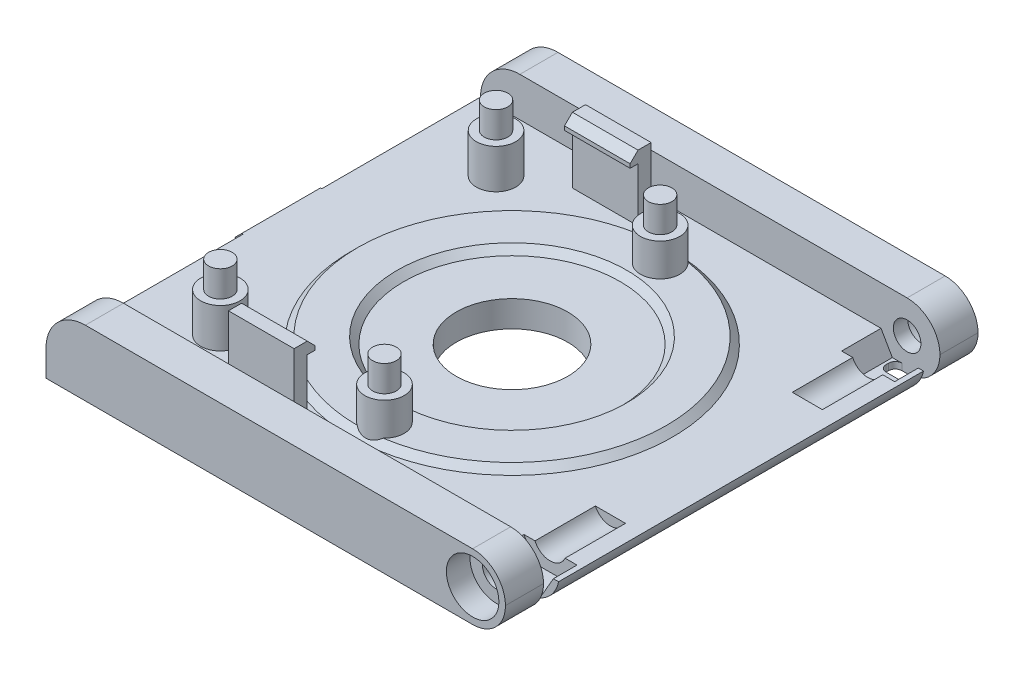
SolidWorks part; units mm, degrees
ref_plane "前视基准面" through (0, 0, 0) normal (0, 0, 1) x (1, 0, 0)
ref_plane "上视基准面" through (0, 0, 0) normal (0, 1, 0) x (1, 0, 0)
ref_plane "右视基准面" through (0, 0, 0) normal (1, 0, 0) x (0, 0, -1)
sketch "zero" plane through (0, 0, 0) normal (0, 1, 0) x (1, 0, 0)
  line L1 (-29.5, 15) -> (29.5, 15)
  line L2 (-32.5, 12) -> (-32.5, -12)
  line L3 (-29.5, -15) -> (29.5, -15)
  line L4 (32.5, 12) -> (32.5, -12)
  line L5 (-32.5, 15) -> (32.5, -15) construction
  line L6 (-32.5, -15) -> (32.5, 15) construction
  line L7 (-25.7, -15) -> (-14.5, -15)
  line L8 (-25.7, -15) -> (-25.7, -9.6569)
  line L9 (-25.7, -9.6569) -> (-14.5, -9.6569)
  line L10 (-14.5, -15) -> (-14.5, -9.6569)
  line L11 (5.2, -15) -> (12.7, -15)
  line L12 (5.2, -15) -> (5.2, -11)
  line L13 (5.2, -11) -> (12.7, -11)
  line L14 (12.7, -15) -> (12.7, -11)
  line L15 (17.8, -15) -> (25.3, -15)
  line L16 (17.8, -15) -> (17.8, -11)
  line L17 (17.8, -11) -> (25.3, -11)
  line L18 (25.3, -15) -> (25.3, -11)
  line L19 (-32.5, 7.7) -> (-19.5, 7.7)
  line L20 (-32.5, 7.7) -> (-32.5, -4.3)
  line L21 (-32.5, -4.3) -> (-19.5, -4.3)
  line L22 (-19.5, 7.7) -> (-19.5, -4.3)
  line L23 (-25.5, 14) -> (25.5, 14)
  line L24 (-25.5, 14) -> (-25.5, 8.8)
  line L25 (-25.5, 8.8) -> (25.5, 8.8)
  line L26 (25.5, 14) -> (25.5, 8.8)
  line L27 (-19.5, 7.2329) -> (-35.5, 7.2329)
  line L28 (-19.5, 7.2329) -> (-19.5, -3.7671)
  line L29 (-19.5, -3.7671) -> (-35.5, -3.7671)
  line L30 (-35.5, 7.2329) -> (-35.5, -3.7671)
  arc A0 (29.5, -15) -> (32.5, -12) centre (29.5, -12) ccw
  arc A1 (29.5, 15) -> (32.5, 12) centre (29.5, 12) cw
  arc A2 (-32.5, -12) -> (-29.5, -15) centre (-29.5, -12) ccw
  arc A3 (-29.5, 15) -> (-32.5, 12) centre (-29.5, 12) ccw
  circle A4 centre (-29, 11.4) radius 3
  circle A5 centre (-29, -11.5) radius 3
  circle A6 centre (29, 11.4) radius 3
  circle A7 centre (29, -11.5) radius 3
  circle A8 centre (-29, 11.4) radius 1.375
  circle A9 centre (-29, -11.5) radius 1.375
  circle A10 centre (29, -11.5) radius 1.375
  circle A11 centre (29, 11.4) radius 1.375
  point P0 (0, 0)
  dimension "D3" = 3
  dimension "D4" = 6
  dimension "D9" = 2.75
  dimension "D1" = 65
  dimension "D2" = 30
  dimension "D5" = 3.6
  dimension "D6" = 3.5
  dimension "D7" = 3.5
  dimension "D8" = 3.5
  dimension "D10" = 12
  dimension "D11" = 7.3
  dimension "D12" = 13
  dimension "D13" = 11.2
  dimension "D14" = 6.8
  dimension "D15" = 19.7
  dimension "D16" = 7.5
  dimension "D17" = 7.5
  dimension "D18" = 5.1
  dimension "D19" = 4
  dimension "D20" = 5.2
  dimension "D21" = 7
  dimension "D22" = 7
  dimension "D23" = 1
  dimension "D24" = 11
  dimension "D25" = 16
sketch "sugar" plane through (0, 0, 0) normal (0, 1, 0) x (1, 0, 0)
  line L1 (-29.5, 15) -> (29.5, 15)
  line L2 (-32.5, 12) -> (-32.5, -12)
  line L3 (-29.5, -15) -> (29.5, -15)
  line L4 (32.5, 12) -> (32.5, -12)
  line L5 (-32.5, 15) -> (32.5, -15) construction
  line L6 (-32.5, -15) -> (32.5, 15) construction
  line L7 (23.5, -11.5) -> (19.5, -11.5)
  line L8 (23.5, -11.5) -> (23.5, -13.9082)
  line L9 (23.5, -13.9082) -> (19.5, -13.9082)
  line L10 (19.5, -11.5) -> (19.5, -13.9082)
  line L11 (16, -11.0071) -> (8.5, -11.0071)
  line L12 (16, -11.0071) -> (16, -15)
  line L13 (16, -15) -> (8.5, -15)
  line L14 (8.5, -11.0071) -> (8.5, -15)
  line L15 (20.5, -13.9082) -> (22.5, -13.9082)
  line L16 (20.5, -13.9082) -> (20.5, -14.8173)
  line L17 (20.5, -14.8173) -> (22.5, -14.8173)
  line L18 (22.5, -13.9082) -> (22.5, -14.8173)
  arc A0 (29.5, 15) -> (32.5, 12) centre (29.5, 12) cw
  arc A1 (29.5, -15) -> (32.5, -12) centre (29.5, -12) ccw
  arc A2 (-32.5, -12) -> (-29.5, -15) centre (-29.5, -12) ccw
  arc A3 (-29.5, 15) -> (-32.5, 12) centre (-29.5, 12) ccw
  circle A4 centre (-29, 11.4) radius 3
  circle A5 centre (-29, 11.4) radius 1.375
  circle A6 centre (-29, -11.5) radius 3
  circle A7 centre (-29, -11.5) radius 1.375
  circle A8 centre (29, 11.4) radius 3
  circle A9 centre (29, 11.4) radius 1.375
  circle A10 centre (29, -11.5) radius 3
  circle A11 centre (29, -11.5) radius 1.375
  dimension "D3" = 3
  dimension "D1" = 65
  dimension "D2" = 30
  dimension "D4" = 9
  dimension "D5" = 4
  dimension "D6" = 3.5
  dimension "D7" = 7.5
  dimension "D8" = 2
  dimension "D9" = 1
sketch "case" plane through (0, 0, 0) normal (0, 1, 0) x (1, 0, 0)
  line L1 (-34.0422, 18) -> (30.9578, 18)
  line L2 (-39.0422, 13) -> (-39.0422, -13)
  line L3 (-34.0422, -18) -> (30.9578, -18)
  line L4 (35.9578, 13) -> (35.9578, -13)
  line L5 (-39.0422, 18) -> (35.9578, -18) construction
  line L6 (-39.0422, -18) -> (35.9578, 18) construction
  arc A0 (-39.0422, -13) -> (-34.0422, -18) centre (-34.0422, -13) ccw
  arc A1 (30.9578, -18) -> (35.9578, -13) centre (30.9578, -13) ccw
  arc A2 (30.9578, 18) -> (35.9578, 13) centre (30.9578, 13) cw
  arc A3 (-34.0422, 18) -> (-39.0422, 13) centre (-34.0422, 13) ccw
  point P0 (-1.5422, 0)
  point P3 (-1.5422, 0)
  dimension "D3" = 5
  dimension "D1" = 75
  dimension "D2" = 36
extrude "凸台-拉伸2" add sketch "case" along normal blind 7
sketch "草图2" plane through (0, 0, 0) normal (0, 1, 0) x (1, 0, 0)
  line L4 (-34.0422, -15.1) -> (30.9578, -15.1)
  line L5 (33.0578, -13) -> (33.0578, 13)
  line L6 (30.9578, 15.1) -> (-34.0422, 15.1)
  line L7 (-36.1422, 13) -> (-36.1422, -13)
  line L12 (33.8578, -13) -> (33.8578, 13)
  line L13 (30.9578, 15.9) -> (-34.0422, 15.9)
  line L14 (-36.9422, 13) -> (-36.9422, -13)
  line L15 (-34.0422, -15.9) -> (30.9578, -15.9)
  arc A4 (30.9578, -15.1) -> (33.0578, -13) centre (30.6746, -12.7168) ccw
  arc A5 (33.0578, 13) -> (30.9578, 15.1) centre (30.6746, 12.7168) ccw
  arc A6 (-34.0422, 15.1) -> (-36.1422, 13) centre (-33.759, 12.7168) ccw
  arc A7 (-36.1422, -13) -> (-34.0422, -15.1) centre (-33.759, -12.7168) ccw
  arc A12 (30.9578, -15.9) -> (33.8578, -13) centre (30.5796, -12.6217) ccw
  arc A13 (33.8578, 13) -> (30.9578, 15.9) centre (30.5796, 12.6217) ccw
  arc A14 (-34.0422, 15.9) -> (-36.9422, 13) centre (-33.6639, 12.6217) ccw
  arc A15 (-36.9422, -13) -> (-34.0422, -15.9) centre (-33.6639, -12.6217) ccw
ref_plane "基准面1" through (0, 7, 0) normal (0, 1, 0) x (1, 0, 0)
sketch "草图3" plane through (0, 7, 0) normal (0, 1, 0) x (1, 0, 0)
  line L4 (-34.0422, -15.1) -> (30.9578, -15.1)
  line L5 (33.0578, -13) -> (33.0578, 13)
  line L6 (30.9578, 15.1) -> (-34.0422, 15.1)
  line L7 (-36.1422, 13) -> (-36.1422, -13)
  line L8 (-34.0422, -15.1) -> (30.9578, -15.1)
  line L9 (33.0578, -13) -> (33.0578, 13)
  line L10 (30.9578, 15.1) -> (-34.0422, 15.1)
  line L11 (-36.1422, 13) -> (-36.1422, -13)
  line L12 (-36.9422, 13) -> (-36.9422, -13)
  line L13 (-34.0422, -15.9) -> (30.9578, -15.9)
  line L14 (33.8578, -13) -> (33.8578, 13)
  line L15 (30.9578, 15.9) -> (-34.0422, 15.9)
  line L16 (-36.9422, 13) -> (-36.9422, -13)
  line L17 (-34.0422, -15.9) -> (30.9578, -15.9)
  line L18 (33.8578, -13) -> (33.8578, 13)
  line L19 (30.9578, 15.9) -> (-34.0422, 15.9)
  arc A4 (30.9578, -15.1) -> (33.0578, -13) centre (30.6746, -12.7168) ccw
  arc A5 (33.0578, 13) -> (30.9578, 15.1) centre (30.6746, 12.7168) ccw
  arc A6 (-34.0422, 15.1) -> (-36.1422, 13) centre (-33.759, 12.7168) ccw
  arc A7 (-36.1422, -13) -> (-34.0422, -15.1) centre (-33.759, -12.7168) ccw
  arc A8 (30.9578, -15.1) -> (33.0578, -13) centre (30.6746, -12.7168) ccw
  arc A9 (33.0578, 13) -> (30.9578, 15.1) centre (30.6746, 12.7168) ccw
  arc A10 (-34.0422, 15.1) -> (-36.1422, 13) centre (-33.759, 12.7168) ccw
  arc A11 (-36.1422, -13) -> (-34.0422, -15.1) centre (-33.759, -12.7168) ccw
  arc A12 (-36.9422, -13) -> (-34.0422, -15.9) centre (-33.6639, -12.6217) ccw
  arc A13 (30.9578, -15.9) -> (33.8578, -13) centre (30.5796, -12.6217) ccw
  arc A14 (33.8578, 13) -> (30.9578, 15.9) centre (30.5796, 12.6217) ccw
  arc A15 (-34.0422, 15.9) -> (-36.9422, 13) centre (-33.6639, 12.6217) ccw
  arc A16 (-36.9422, -13) -> (-34.0422, -15.9) centre (-33.6639, -12.6217) ccw
  arc A17 (30.9578, -15.9) -> (33.8578, -13) centre (30.5796, -12.6217) ccw
  arc A18 (33.8578, 13) -> (30.9578, 15.9) centre (30.5796, 12.6217) ccw
  arc A19 (-34.0422, 15.9) -> (-36.9422, 13) centre (-33.6639, 12.6217) ccw
  dimension "D1" = 0
  dimension "D2" = 0
extrude "凸台-拉伸4" add sketch "草图3" along normal blind 1
ref_plane "基准面3" through (33.8578, 0, 0) normal (1, 0, 0) x (0, 0, -1)
sketch "草图7" plane through (0, 7, 0) normal (0, 1, 0) x (1, 0, 0)
  line L0 (-36.9422, 13) -> (-36.9422, -13) construction
  line L1 (-36.9422, 5) -> (-36.1422, 5)
  line L2 (-36.9422, 5) -> (-36.9422, -5)
  line L3 (-36.9422, -5) -> (-36.1422, -5)
  line L4 (-36.1422, 5) -> (-36.1422, -5)
  line L5 (-36.1422, 13) -> (-36.1422, -13) construction
  point P10 (-36.1422, 0)
  dimension "D1" = 5
  dimension "D2" = 10
extrude "凸台-拉伸8" add sketch "草图7" along normal blind 2.8
ref_plane "基准面5" through (0, 0, 5) normal (0, 0, 1) x (1, 0, 0)
sketch "草图8" plane through (0, 0, 5) normal (0, 0, 1) x (1, 0, 0)
  line L0 (-34.0422, 7) -> (-39.0422, 7) construction
  line L1 (-36.9422, 9.8) -> (-36.9422, 8) construction
  circle A0 centre (-36.6922, 8.6) radius 0.7
  dimension "D1" = 1.4
  dimension "D2" = 1.6
  dimension "D3" = 0.25
extrude "凸台-拉伸9" add sketch "草图8" against normal blind 10
fillet "圆角3" radius 0.5 1 edges at (-36.9422, 9.8, 0)
sketch "草图13" plane through (0, 8, 0) normal (0, 1, 0) x (1, 0, 0)
  line L0 (-36.9422, -5) -> (-36.9422, -13) construction
  line L1 (-36.1422, -5) -> (-36.9422, -5)
  line L2 (-36.1422, -5) -> (-36.1422, -7)
  line L3 (-36.1422, -7) -> (-36.9422, -7)
  line L4 (-36.9422, -5) -> (-36.9422, -7)
  line L5 (-36.9422, 13) -> (-36.9422, 5) construction
  line L6 (-36.1422, 5) -> (-36.9422, 5)
  line L7 (-36.1422, 5) -> (-36.1422, 7)
  line L8 (-36.1422, 7) -> (-36.9422, 7)
  line L9 (-36.9422, 5) -> (-36.9422, 7)
  dimension "D1" = 2
  dimension "D2" = 2
extrude "切除-拉伸2" cut sketch "草图13" against normal blind 1
sketch "草图15" plane through (0, 7, 0) normal (0, 1, 0) x (1, 0, 0)
  line L4 (-34.0422, -15.1) -> (30.9578, -15.1)
  line L5 (33.0578, -13) -> (33.0578, 13)
  line L6 (30.9578, 15.1) -> (-34.0422, 15.1)
  line L7 (-36.1422, 13) -> (-36.1422, -13)
  line L8 (-34.0422, -15.1) -> (30.9578, -15.1)
  line L9 (33.0578, -13) -> (33.0578, 13)
  line L10 (30.9578, 15.1) -> (-34.0422, 15.1)
  line L11 (-36.1422, 13) -> (-36.1422, -13)
  arc A4 (30.9578, -15.1) -> (33.0578, -13) centre (30.6746, -12.7168) ccw
  arc A5 (33.0578, 13) -> (30.9578, 15.1) centre (30.6746, 12.7168) ccw
  arc A6 (-34.0422, 15.1) -> (-36.1422, 13) centre (-33.759, 12.7168) ccw
  arc A7 (-36.1422, -13) -> (-34.0422, -15.1) centre (-33.759, -12.7168) ccw
  arc A8 (30.9578, -15.1) -> (33.0578, -13) centre (30.6746, -12.7168) ccw
  arc A9 (33.0578, 13) -> (30.9578, 15.1) centre (30.6746, 12.7168) ccw
  arc A10 (-34.0422, 15.1) -> (-36.1422, 13) centre (-33.759, 12.7168) ccw
  arc A11 (-36.1422, -13) -> (-34.0422, -15.1) centre (-33.759, -12.7168) ccw
  dimension "D1" = 0
extrude "切除-拉伸3" cut sketch "草图15" against normal blind 5
sketch "草图19" plane through (0, 2, 0) normal (0, 1, 0) x (1, 0, 0)
  line L0 (30.9578, 18) -> (-34.0422, 18) construction
  circle A0 centre (-1.5422, 0) radius 4.25
  point P5 (-1.5422, 18)
  dimension "D1" = 8.5
extrude "切除-拉伸4" cut sketch "草图19" against normal blind 3
sketch "草图21" plane through (0, 2, 0) normal (0, 1, 0) x (1, 0, 0)
  line L0 (-34.0422, -15.1) -> (30.9578, -15.1) construction
  line L1 (30.9578, 15.1) -> (-34.0422, 15.1) construction
  line L5 (30.9578, 15.1) -> (-34.0422, 15.1) construction
  line L6 (-34.0422, -15.1) -> (30.9578, -15.1) construction
  circle A0 centre (-13.2575, 10.5) radius 1.5
  circle A1 centre (-0.7575, 10.5) radius 1.5
  circle A2 centre (-13.2575, -10.5) radius 1.5
  circle A3 centre (-0.7575, -10.5) radius 1.5
  circle A4 centre (-1.5422, 0) radius 4.25 construction
  dimension "D1" = 3
  dimension "D2" = 12.5
  dimension "D3" = 12.5
  dimension "D4" = 4.6
  dimension "D5" = 4.6
  dimension "D7" = 11.7153
  dimension "D8" = 4.6
  dimension "D9" = 4.6
extrude "凸台-拉伸11" add sketch "草图21" along normal blind 3
sketch "草图22" plane through (0, 5, 0) normal (0, 1, 0) x (1, 0, 0)
  circle A0 centre (-13.2575, -10.5) radius 0.9
  circle A1 centre (-0.7575, -10.5) radius 0.9
  circle A2 centre (-13.2575, 10.5) radius 0.9
  circle A3 centre (-0.7575, 10.5) radius 0.9
  circle A4 centre (-13.2575, 10.5) radius 1.5 construction
  circle A5 centre (-13.2575, -10.5) radius 1.5 construction
  circle A6 centre (-0.7575, -10.5) radius 1.5 construction
  circle A7 centre (-0.7575, 10.5) radius 1.5 construction
  dimension "D1" = 1.8
extrude "凸台-拉伸12" add sketch "草图22" along normal blind 2
sketch "草图28" plane through (0, 2, 0) normal (0, 1, 0) x (1, 0, 0)
  line L0 (30.9578, 15.1) -> (-34.0422, 15.1) construction
  line L1 (-4.5422, -12.6) -> (-9.5422, -12.6)
  line L2 (-4.5422, -12.6) -> (-4.5422, -13.6)
  line L3 (-4.5422, -13.6) -> (-9.5422, -13.6)
  line L4 (-9.5422, -12.6) -> (-9.5422, -13.6)
  line L5 (-4.5422, 13.6) -> (-9.5422, 13.6)
  line L6 (-4.5422, 13.6) -> (-4.5422, 12.6)
  line L7 (-4.5422, 12.6) -> (-9.5422, 12.6)
  line L8 (-9.5422, 13.6) -> (-9.5422, 12.6)
  line L9 (-34.0422, -15.1) -> (30.9578, -15.1) construction
  circle A0 centre (-1.5422, 0) radius 4.25 construction
  dimension "D1" = 1
  dimension "D2" = 1.5
  dimension "D3" = 5
  dimension "D4" = 1.5
  dimension "D5" = 3
extrude "凸台-拉伸16" add sketch "草图28" along normal blind 5
fillet "圆角4" radius 1 2 edges at (-7.0422, 2, -13.6) (-7.0422, 2, 13.6)
sketch "草图29" plane through (0, 0, 12.6) normal (0, 0, -1) x (-1, 0, 0)
  line L0 (9.5422, 7) -> (9.5422, 2) construction
  line L1 (4.5422, 7) -> (9.5422, 7)
  line L2 (4.5422, 7) -> (4.5422, 6.1)
  line L3 (4.5422, 6.1) -> (9.5422, 6.1)
  line L4 (9.5422, 7) -> (9.5422, 6.1)
  dimension "D1" = 0.9
extrude "凸台-拉伸17" add sketch "草图29" along normal blind 0.6
sketch "草图30" plane through (0, 0, -12.6) normal (0, 0, 1) x (1, 0, 0)
  line L0 (-4.5422, 7) -> (-4.5422, 2) construction
  line L1 (-9.5422, 7) -> (-4.5422, 7)
  line L2 (-9.5422, 7) -> (-9.5422, 6.1)
  line L3 (-9.5422, 6.1) -> (-4.5422, 6.1)
  line L4 (-4.5422, 7) -> (-4.5422, 6.1)
  dimension "D1" = 0.9
extrude "凸台-拉伸18" add sketch "草图30" along normal blind 0.6
chamfer "倒角5" distance 0.6 angle 45 2 edges at (-7.0422, 7, -12) (-7.0422, 7, 12)
sketch "草图32" plane through (0, 0, 0) normal (0, 1, 0) x (1, 0, 0)
  line L75 (-14.6761, -9.5363) -> (-15.4836, -9.6938)
  line L76 (-12.4748, -8.5613) -> (-14.1869, -8.5613)
  line L77 (-12.4748, -7.6298) -> (-12.4748, -8.5613)
  line L78 (-15.4702, -7.6298) -> (-12.4748, -7.6298)
  line L79 (-15.4702, -8.3938) -> (-15.4702, -7.6298)
  line L80 (-14.9509, -8.4574) -> (-15.4702, -8.3938)
  line L81 (-14.9509, -8.4776) -> (-14.9509, -8.4574)
  line L82 (-13.8452, -6.0752) -> (-13.366, -6.0752)
  line L83 (-12.4748, -7.0133) -> (-14.1769, -7.0133)
  line L84 (-12.4748, -6.2494) -> (-12.4748, -7.0133)
  line L85 (-12.7763, -6.1824) -> (-12.4748, -6.2494)
  line L86 (-12.7763, -6.1589) -> (-12.7763, -6.1824)
  line L87 (-15.1519, -4.5104) -> (-14.5354, -4.8388)
  line L88 (-12.3475, -2.6743) -> (-12.3475, -2.9592)
  line L89 (-12.5853, -1.763) -> (-12.5586, -1.763)
  line L90 (-13.681, -1.8199) -> (-13.6609, -1.8199)
  line L91 (-15.4702, -4.2424) -> (-15.4702, -3.1434)
  line L92 (-14.7934, -4.2424) -> (-15.4702, -4.2424)
  line L93 (-14.7934, -3.78) -> (-14.7934, -4.2424)
  line L94 (-13.0645, -3.1367) -> (-13.0645, -2.6643)
  line L95 (-15.4702, -0.8717) -> (-15.4702, 0.0664)
  line L96 (-12.4748, -0.8717) -> (-15.4702, -0.8717)
  line L97 (-12.4748, -0.1078) -> (-12.4748, -0.8717)
  line L98 (-12.8869, -0.0408) -> (-12.4748, -0.1078)
  line L99 (-12.8869, -0.0207) -> (-12.8869, -0.0408)
  line L100 (-15.4702, 1.849) -> (-13.6173, 1.849)
  line L101 (-15.4702, 0.9141) -> (-15.4702, 1.849)
  line L102 (-13.7346, 0.9141) -> (-15.4702, 0.9141)
  line L103 (-15.4702, 0.0664) -> (-13.5068, 0.0664)
  line L104 (-13.614, 4.7204) -> (-12.964, 5.2531)
  line L105 (-14.207, 4.3083) -> (-13.9959, 3.809)
  line L106 (-15.3596, 2.8776) -> (-15.9493, 2.4085)
  line L107 (-14.7029, 3.0686) -> (-14.8973, 3.5577)
  line L108 (-15.3362, 5.8361) -> (-15.3362, 6.3153)
  line L109 (-12.4748, 5.8361) -> (-15.3362, 5.8361)
  line L110 (-12.4748, 6.3153) -> (-12.4748, 5.8361)
  line L111 (-15.3362, 6.3153) -> (-12.4748, 6.3153)
  line L112 (-15.9393, 9.0091) -> (-15.9393, 8.4529)
  line L113 (-14.4014, 9.0091) -> (-15.9393, 9.0091)
  line L114 (-14.4014, 8.4328) -> (-14.4014, 9.0091)
  line L115 (-14.006, 9.0091) -> (-14.006, 8.3692)
  line L116 (-12.4748, 9.0091) -> (-14.006, 9.0091)
  line L117 (-12.4748, 9.4984) -> (-12.4748, 9.0091)
  line L118 (-16.3346, 9.4984) -> (-12.4748, 9.4984)
  line L119 (-16.3346, 8.396) -> (-16.3346, 9.4984)
  spline S0 degree 3 poles (-15.4836, -9.6938) (-15.5205, -9.61) (-15.5439, -9.5095) (-15.5439, -9.3319) knots 10 10 10 10 11 11 11 11
  spline S1 degree 3 poles (-14.723, -9.208) (-14.723, -9.342) (-14.7029, -9.4291) (-14.6761, -9.5363) knots 8 8 8 8 9 9 9 9
  spline S2 degree 3 poles (-14.1869, -8.5613) (-14.5823, -8.7188) (-14.723, -8.9869) (-14.723, -9.208) knots 7 7 7 7 8 8 8 8
  spline S3 degree 3 poles (-15.5439, -9.3319) (-15.5439, -9.0304) (-15.3496, -8.6987) (-14.9509, -8.4776) knots 0 0 0 0 1 1 1 1
  spline S4 degree 3 poles (-13.3861, -5.3012) (-13.5972, -5.3012) (-13.7648, -5.4922) (-13.8452, -6.0752) knots 2 2 2 2 3 3 3 3
  spline S5 degree 3 poles (-13.1282, -5.6229) (-13.1282, -5.4285) (-13.2119, -5.3012) (-13.3861, -5.3012) knots 1 1 1 1 2 2 2 2
  spline S6 degree 3 poles (-13.366, -6.0752) (-13.2186, -5.9378) (-13.1282, -5.8138) (-13.1282, -5.6229) knots 0 0 0 0 1 1 1 1
  spline S7 degree 3 poles (-14.1769, -7.0133) (-15.1151, -7.0133) (-15.5439, -6.5744) (-15.5439, -5.8004) knots 11 11 11 11 12 12 12 12
  spline S8 degree 3 poles (-12.4011, -5.3012) (-12.4011, -5.6329) (-12.5552, -5.911) (-12.7763, -6.1589) knots 6 6 6 6 7 7 7 7
  spline S9 degree 3 poles (-13.3124, -4.4099) (-12.8132, -4.4099) (-12.4011, -4.7483) (-12.4011, -5.3012) knots 5 5 5 5 6 6 6 6
  spline S10 degree 3 poles (-14.4148, -6.0752) (-14.2874, -4.9058) (-13.9457, -4.4099) (-13.3124, -4.4099) knots 4 4 4 4 5 5 5 5
  spline S11 degree 3 poles (-14.7967, -5.6229) (-14.7967, -5.9277) (-14.656, -6.0551) (-14.4148, -6.0752) knots 3 3 3 3 4 4 4 4
  spline S12 degree 3 poles (-14.5354, -4.8388) (-14.7029, -5.137) (-14.7967, -5.385) (-14.7967, -5.6229) knots 2 2 2 2 3 3 3 3
  spline S13 degree 3 poles (-15.5439, -5.8004) (-15.5439, -5.3347) (-15.3864, -4.9058) (-15.1519, -4.5104) knots 0 0 0 0 1 1 1 1
  spline S14 degree 3 poles (-12.133, -3.3947) (-11.942, -3.3947) (-11.8013, -3.1267) (-11.8013, -2.7413) knots 5 5 5 5 6 6 6 6
  spline S15 degree 3 poles (-12.3475, -2.9592) (-12.3475, -3.2372) (-12.3106, -3.3947) (-12.133, -3.3947) knots 4 4 4 4 5 5 5 5
  spline S16 degree 3 poles (-12.3843, -2.2454) (-12.3575, -2.3426) (-12.3475, -2.4566) (-12.3475, -2.6743) knots 2 2 2 2 3 3 3 3
  spline S17 degree 3 poles (-12.1163, -2.1047) (-12.2168, -2.1047) (-12.3006, -2.1516) (-12.3843, -2.2454) knots 1 1 1 1 2 2 2 2
  spline S18 degree 3 poles (-11.8013, -2.7413) (-11.8013, -2.356) (-11.9052, -2.1047) (-12.1163, -2.1047) knots 0 0 0 0 1 1 1 1
  spline S19 degree 3 poles (-14.9174, -2.6676) (-14.9174, -2.8888) (-14.7599, -3.0462) (-14.455, -3.0462) (-14.1434, -3.0462) (-13.9859, -2.8888) (-13.9859, -2.6676) knots 0 0 0 0 1 1 1 2 2 2 2
  spline S20 degree 3 poles (-13.9859, -2.6676) (-13.9859, -2.4532) (-14.1434, -2.289) (-14.455, -2.289) (-14.7599, -2.289) (-14.9174, -2.4532) (-14.9174, -2.6676) knots 2 2 2 2 3 3 3 4 4 4 4
  spline S21 degree 3 poles (-12.2972, -4.2893) (-12.84, -4.2893) (-13.0645, -3.8739) (-13.0645, -3.1367) knots 19 19 19 19 20 20 20 20
  spline S22 degree 3 poles (-11.215, -2.5939) (-11.215, -3.6359) (-11.6639, -4.2893) (-12.2972, -4.2893) knots 18 18 18 18 19 19 19 19
  spline S23 degree 3 poles (-11.9688, -1.3374) (-11.4328, -1.3374) (-11.215, -1.9037) (-11.215, -2.5939) knots 17 17 17 17 18 18 18 18
  spline S24 degree 3 poles (-12.5586, -1.763) (-12.4178, -1.4849) (-12.2168, -1.3374) (-11.9688, -1.3374) knots 16 16 16 16 17 17 17 17
  spline S25 degree 3 poles (-13.1013, -1.4882) (-12.8501, -1.4882) (-12.6926, -1.6055) (-12.5853, -1.763) knots 14 14 14 14 15 15 15 15
  spline S26 degree 3 poles (-13.6609, -1.8199) (-13.5235, -1.6256) (-13.3124, -1.4882) (-13.1013, -1.4882) knots 13 13 13 13 14 14 14 14
  spline S27 degree 3 poles (-14.455, -1.4145) (-14.1065, -1.4145) (-13.8284, -1.6089) (-13.681, -1.8199) knots 11 11 11 11 12 12 12 12
  spline S28 degree 3 poles (-15.5439, -2.6676) (-15.5439, -2.021) (-15.1888, -1.4145) (-14.455, -1.4145) knots 10 10 10 10 11 11 11 11
  spline S86 degree 3 poles (-15.4702, -3.1434) (-15.5205, -3.006) (-15.5439, -2.8419) (-15.5439, -2.6676) knots 9 9 9 9 10 10 10 10
  spline S87 degree 3 poles (-14.4282, -3.8638) (-14.5723, -3.8638) (-14.7096, -3.8269) (-14.7934, -3.78) knots 5 5 5 5 6 6 6 6
  spline S88 degree 3 poles (-13.423, -2.6676) (-13.423, -3.331) (-13.7279, -3.8638) (-14.4282, -3.8638) knots 4 4 4 4 5 5 5 5
  spline S89 degree 3 poles (-13.4766, -2.3158) (-13.4398, -2.4465) (-13.423, -2.5671) (-13.423, -2.6676) knots 3 3 3 3 4 4 4 4
  spline S90 degree 3 poles (-13.2655, -2.222) (-13.366, -2.222) (-13.4129, -2.2454) (-13.4766, -2.3158) knots 2 2 2 2 3 3 3 3
  spline S91 degree 3 poles (-13.0645, -2.6643) (-13.0645, -2.3426) (-13.1282, -2.222) (-13.2655, -2.222) knots 1 1 1 1 2 2 2 2
  spline S92 degree 3 poles (-12.4011, 0.9175) (-12.4011, 0.5087) (-12.5921, 0.2272) (-12.8869, -0.0207) knots 7 7 7 7 8 8 8 8
  spline S93 degree 3 poles (-13.6173, 1.849) (-12.8702, 1.849) (-12.4011, 1.5708) (-12.4011, 0.9175) knots 6 6 6 6 7 7 7 7
  spline S94 degree 3 poles (-13.2019, 0.5657) (-13.2019, 0.8036) (-13.3191, 0.9141) (-13.7346, 0.9141) knots 2 2 2 2 3 3 3 3
  spline S95 degree 3 poles (-13.5068, 0.0664) (-13.2856, 0.2239) (-13.2019, 0.3546) (-13.2019, 0.5657) knots 1 1 1 1 2 2 2 2
  spline S96 degree 3 poles (-13.6274, 2.2913) (-14.1802, 2.2913) (-14.5086, 2.5827) (-14.7029, 3.0686) knots 15 15 15 15 16 16 16 16
  spline S97 degree 3 poles (-12.4011, 3.789) (-12.4011, 2.8407) (-12.974, 2.2913) (-13.6274, 2.2913) knots 14 14 14 14 15 15 15 15
  spline S98 degree 3 poles (-12.964, 5.2531) (-12.5921, 4.8477) (-12.4011, 4.2983) (-12.4011, 3.789) knots 13 13 13 13 14 14 14 14
  spline S99 degree 3 poles (-13.2119, 3.7688) (-13.2119, 4.0771) (-13.3761, 4.4423) (-13.614, 4.7204) knots 11 11 11 11 12 12 12 12
  spline S100 degree 3 poles (-13.5537, 3.2562) (-13.3426, 3.2562) (-13.2119, 3.4204) (-13.2119, 3.7688) knots 10 10 10 10 11 11 11 11
  spline S101 degree 3 poles (-13.9959, 3.809) (-13.8552, 3.474) (-13.7815, 3.2562) (-13.5537, 3.2562) knots 9 9 9 9 10 10 10 10
  spline S102 degree 3 poles (-15.2826, 5.1057) (-14.713, 5.1057) (-14.3712, 4.7204) (-14.207, 4.3083) knots 7 7 7 7 8 8 8 8
  spline S103 degree 3 poles (-16.4687, 3.6817) (-16.4687, 4.516) (-15.9393, 5.1057) (-15.2826, 5.1057) knots 6 6 6 6 7 7 7 7
  spline S104 degree 3 poles (-15.9493, 2.4085) (-16.2944, 2.7502) (-16.4687, 3.2294) (-16.4687, 3.6817) knots 5 5 5 5 6 6 6 6
  spline S105 degree 3 poles (-15.6612, 3.6817) (-15.6612, 3.3768) (-15.5573, 3.1356) (-15.3596, 2.8776) knots 3 3 3 3 4 4 4 4
  spline S106 degree 3 poles (-15.3362, 4.1508) (-15.5439, 4.1508) (-15.6612, 3.9732) (-15.6612, 3.6817) knots 2 2 2 2 3 3 3 3
  spline S107 degree 3 poles (-14.8973, 3.5577) (-15.0346, 3.9029) (-15.1184, 4.1508) (-15.3362, 4.1508) knots 1 1 1 1 2 2 2 2
  spline S108 degree 3 poles (-16.5457, 6.074) (-16.5457, 6.265) (-16.4318, 6.4057) (-16.2341, 6.4057) (-16.0566, 6.4057) (-15.9259, 6.265) (-15.9259, 6.074) knots 0 0 0 0 1 1 1 2 2 2 2
  spline S109 degree 3 poles (-15.9259, 6.074) (-15.9259, 5.8831) (-16.0566, 5.7423) (-16.2341, 5.7423) (-16.4318, 5.7423) (-16.5457, 5.8831) (-16.5457, 6.074) knots 2 2 2 2 3 3 3 4 4 4 4
  spline S110 degree 3 poles (-15.2022, 7.4343) (-14.6493, 7.4343) (-14.4014, 7.7527) (-14.4014, 8.4328) knots 4 4 4 4 5 5 5 5
  spline S111 degree 3 poles (-15.9393, 8.4529) (-15.9393, 7.7761) (-15.7617, 7.4343) (-15.2022, 7.4343) knots 3 3 3 3 4 4 4 4
  spline S112 degree 3 poles (-15.2022, 6.9485) (-16.0465, 6.9485) (-16.3346, 7.5282) (-16.3346, 8.396) knots 6 6 6 6 7 7 7 7
  spline S113 degree 3 poles (-14.006, 8.3692) (-14.006, 7.5282) (-14.388, 6.9485) (-15.2022, 6.9485) knots 5 5 5 5 6 6 6 6
sketch "草图33" plane through (0, 0, 0) normal (0, -1, 0) x (1, 0, 0)
  line L0 (31.4528, 12.8823) -> (31.1283, 13.0694)
  line L1 (31.1283, 13.0694) -> (29.4447, 14.0408)
  line L2 (29.4447, 14.0408) -> (29.1201, 14.2301)
  line L3 (28.4395, 14.2301) -> (28.1149, 14.0408)
  line L4 (28.1149, 14.0408) -> (26.4313, 13.0694)
  line L5 (26.4313, 13.0694) -> (26.1067, 12.8823)
  line L6 (25.7664, 12.2941) -> (25.7664, 9.5985)
  line L7 (26.1067, 9.0102) -> (26.4313, 8.8231)
  line L8 (26.4313, 8.8231) -> (28.1149, 7.8517)
  line L9 (28.1149, 7.8517) -> (28.4395, 7.6624)
  line L10 (29.1201, 7.6624) -> (29.4447, 7.8517)
  line L11 (29.4447, 7.8517) -> (31.1283, 8.8231)
  line L12 (31.1283, 8.8231) -> (31.4528, 9.0102)
  line L13 (31.7932, 9.5985) -> (31.7932, 12.2941)
  line L14 (26.5395, 12.6141) -> (28.622, 13.8177)
  line L15 (28.9398, 13.8177) -> (31.0111, 12.6118)
  line L16 (31.0134, 12.3346) -> (29.0007, 11.1311)
  line L17 (29.625, 9.0913) -> (29.3906, 8.9606)
  line L18 (29.368, 8.9223) -> (29.368, 8.2461)
  line L19 (29.3455, 8.2078) -> (28.9083, 7.9599)
  line L20 (28.8429, 7.9982) -> (28.8429, 10.0853)
  line L21 (28.8654, 10.1236) -> (29.6092, 10.5451)
  line L22 (31.1689, 9.2311) -> (30.7361, 8.9854)
  line L23 (30.6708, 9.0237) -> (30.6708, 10.0177)
  line L24 (30.6933, 10.056) -> (31.126, 10.2994)
  line L25 (31.1914, 10.2611) -> (31.1914, 9.2694)
  line L26 (29.5979, 9.4925) -> (29.3906, 9.3888)
  line L27 (29.368, 9.4362) -> (29.368, 9.9681)
  line L28 (29.3906, 10.0064) -> (29.5844, 10.1146)
  line L29 (29.3906, 9.3888) -> (29.3906, 8.9606)
  line L30 (29.368, 9.4362) -> (29.368, 8.9223)
  spline S0 degree 3 poles (29.1201, 14.2301) (29.0142, 14.2887) (28.897, 14.3203) (28.7798, 14.3203) knots 3 3 3 3 4 4 4 4
  spline S1 degree 3 poles (28.7798, 14.3203) (28.6626, 14.3203) (28.5454, 14.2887) (28.4395, 14.2301) knots 4 4 4 4 5 5 5 5
  spline S2 degree 3 poles (26.1067, 12.8823) (25.8971, 12.7606) (25.7664, 12.5352) (25.7664, 12.2941) knots 8 8 8 8 9 9 9 9
  spline S3 degree 3 poles (25.7664, 9.5985) (25.7664, 9.355) (25.8971, 9.1319) (26.1067, 9.0102) knots 10 10 10 10 11 11 11 11
  spline S4 degree 3 poles (28.4395, 7.6624) (28.5454, 7.6015) (28.6626, 7.5722) (28.7798, 7.5722) knots 14 14 14 14 15 15 15 15
  spline S5 degree 3 poles (28.7798, 7.5722) (28.897, 7.5722) (29.0142, 7.6015) (29.1201, 7.6624) knots 15 15 15 15 16 16 16 16
  spline S6 degree 3 poles (31.4528, 9.0102) (31.6647, 9.1319) (31.7932, 9.355) (31.7932, 9.5985) knots 19 19 19 19 20 20 20 20
  spline S7 degree 3 poles (31.7932, 12.2941) (31.7932, 12.5352) (31.6647, 12.7606) (31.4528, 12.8823) knots 21 21 21 21 22 22 22 22
  spline S8 degree 2 poles (28.5612, 11.1311) (26.5237, 12.3076) (26.5192, 12.3098) knots 0 0 0 1 1 1
  spline S9 degree 3 poles (26.5192, 12.3098) (26.4133, 12.3865) (26.4245, 12.5487) (26.5395, 12.6141) knots 1 1 1 1 2 2 2 2
  spline S10 degree 3 poles (28.622, 13.8177) (28.719, 13.874) (28.8407, 13.874) (28.9398, 13.8177) knots 3 3 3 3 4 4 4 4
  spline S11 degree 3 poles (31.0111, 12.6118) (31.117, 12.551) (31.1193, 12.3977) (31.0134, 12.3346) knots 5 5 5 5 6 6 6 6
  spline S12 degree 3 poles (29.0007, 11.1311) (28.8654, 11.0522) (28.6964, 11.0522) (28.5612, 11.1311) knots 7 7 7 7 8 8 8 8
  spline S13 degree 3 poles (29.368, 8.2461) (29.368, 8.2304) (29.3613, 8.2168) (29.3455, 8.2078) knots 3 3 3 3 4 4 4 4
  spline S14 degree 3 poles (28.9083, 7.9599) (28.879, 7.9441) (28.8429, 7.9644) (28.8429, 7.9982) knots 5 5 5 5 6 6 6 6
  spline S15 degree 3 poles (28.8429, 10.0853) (28.8429, 10.1011) (28.8497, 10.1168) (28.8654, 10.1236) knots 7 7 7 7 8 8 8 8
  spline S16 degree 3 poles (29.6092, 10.5451) (30.0915, 10.8178) (30.4904, 10.8719) (30.4904, 10.331) knots 9 9 9 9 10 10 10 10
  spline S17 degree 3 poles (30.4904, 10.331) (30.4904, 9.8103) (30.087, 9.3528) (29.625, 9.0913) knots 10 10 10 10 11 11 11 11
  spline S18 degree 3 poles (31.1914, 9.2694) (31.1914, 9.2536) (31.1824, 9.2378) (31.1689, 9.2311) knots 0 0 0 0 1 1 1 1
  spline S19 degree 3 poles (30.7361, 8.9854) (30.7068, 8.9696) (30.6708, 8.9899) (30.6708, 9.0237) knots 2 2 2 2 3 3 3 3
  spline S20 degree 3 poles (30.6708, 10.0177) (30.6708, 10.0334) (30.6798, 10.047) (30.6933, 10.056) knots 4 4 4 4 5 5 5 5
  spline S21 degree 3 poles (31.126, 10.2994) (31.1553, 10.3152) (31.1914, 10.2949) (31.1914, 10.2611) knots 6 6 6 6 7 7 7 7
  spline S22 degree 3 poles (30.9322, 10.9598) (31.1058, 11.059) (31.2297, 11.0161) (31.2297, 10.8584) (31.2297, 10.7028) (31.1058, 10.5203) (30.9322, 10.4234) knots 2 2 2 2 3 3 3 4 4 4 4
  spline S23 degree 3 poles (30.9322, 10.4234) (30.7564, 10.3219) (30.6325, 10.3648) (30.6325, 10.5203) (30.6325, 10.6803) (30.7564, 10.8606) (30.9322, 10.9598) knots 0 0 0 0 1 1 1 2 2 2 2
  spline S24 degree 3 poles (29.9766, 10.0402) (29.9766, 9.8261) (29.8549, 9.6368) (29.5979, 9.4925) knots 0 0 0 0 1 1 1 1
  spline S25 degree 3 poles (29.368, 9.9681) (29.368, 9.9839) (29.3771, 9.9996) (29.3906, 10.0064) knots 4 4 4 4 5 5 5 5
  spline S26 degree 3 poles (29.5844, 10.1146) (29.8369, 10.2588) (29.9766, 10.2611) (29.9766, 10.0402) knots 6 6 6 6 7 7 7 7
extrude "切除-拉伸5" cut sketch "草图33" against normal blind 0.5
sketch "草图34" plane through (0, 8, 0) normal (0, 1, 0) x (1, 0, 0)
  line L0 (33.8578, -13) -> (33.8578, 13) construction
  line L1 (33.8578, -6) -> (33.0578, -6)
  line L2 (33.8578, -6) -> (33.8578, 6)
  line L3 (33.8578, 6) -> (33.0578, 6)
  line L4 (33.0578, -6) -> (33.0578, 6)
  line L5 (33.0578, -13) -> (33.0578, 13) construction
  line L6 (35.9578, -13) -> (35.9578, 13) construction
  point P8 (33.0578, 0)
  point P11 (35.9578, 0)
  dimension "D1" = 12
extrude "切除-拉伸6" cut sketch "草图34" against normal blind 1
sketch "草图35" plane through (0, 7, 0) normal (0, 1, 0) x (1, 0, 0)
  line L0 (33.0578, 6) -> (33.0578, -6) construction
  line L1 (33.0578, -5) -> (33.8578, -5)
  line L2 (33.0578, -5) -> (33.0578, 5)
  line L3 (33.0578, 5) -> (33.8578, 5)
  line L4 (33.8578, -5) -> (33.8578, 5)
  line L5 (35.9578, -13) -> (35.9578, 13) construction
  point P6 (33.8578, 0)
  point P9 (35.9578, 0)
  dimension "D1" = 10
  dimension "D2" = 0.8
extrude "凸台-拉伸19" add sketch "草图35" along normal blind 2.8
sketch "草图36" plane through (0, 0, -5) normal (0, 0, -1) x (-1, 0, 0)
  line L0 (-30.9578, 7) -> (-35.9578, 7) construction
  line L1 (-33.8578, 9.8) -> (-33.8578, 7) construction
  circle A0 centre (-33.6096, 8.6) radius 0.7
  dimension "D1" = 1.4
  dimension "D2" = 1.6
  dimension "D3" = 0.2482
extrude "凸台-拉伸20" add sketch "草图36" against normal blind 10
fillet "圆角5" radius 0.5 1 edges at (33.8578, 9.8, 0)
fillet "圆角6" radius 1 4 edges at (33.4578, 8, -6) (33.4578, 8, 6) (-36.5422, 8, 7) (-36.5422, 8, -7)
sketch "草图37" plane through (0, 0, 0) normal (0, -1, 0) x (1, 0, 0)
  circle A0 centre (-1.5422, 0) radius 11.75
  circle A1 centre (-1.5422, 0) radius 4.25 construction
  circle A2 centre (-1.5422, 0) radius 9.25
  dimension "D1" = 23.5
  dimension "D2" = 18.5
extrude "切除-拉伸7" cut sketch "草图37" against normal blind 1.5
chamfer "倒角6" distance 1.2 angle 45 1 edges at (-1.5422, 0, -9.25)
chamfer "倒角7" distance 0.5 angle 45 1 edges at (-1.5422, 0, -11.75)
sketch "草图38" plane through (0, 2, 0) normal (0, 1, 0) x (1, 0, 0)
  circle A1 centre (-1.5422, 0) radius 8.25
  circle A2 centre (-1.5422, 0) radius 12.25
  circle A3 centre (-1.5422, 0) radius 4.25 construction
  dimension "D2" = 4
  dimension "D1" = 24.5
extrude "凸台-拉伸21" add sketch "草图38" along normal blind 0.5
chamfer "倒角8" distance 0.5 angle 45 2 edges at (-1.5422, 2.5, 8.25) (-1.5422, 2.5, 12.25)
ref_plane "基准面7" through (-36.9422, 0, 0) normal (-1, 0, 0) x (0, 0, 1)
ref_plane "基准面8" through (0, 0, 0) normal (0, -1, 0) x (-1, 0, 0)
sketch "草图12" plane through (0, 0, 0) normal (0, -1, 0) x (-1, 0, 0)
  line L76 (34.0422, -18) -> (-30.9578, -18) construction
  line L78 (39.0422, 13) -> (39.0422, -13) construction
  line B0 (-8.1993, 5.026) -> (-9.0198, 5.499)
  line B1 (-9.0198, 5.499) -> (-13.2767, 7.9551)
  line B2 (-13.2767, 7.9551) -> (-14.0973, 8.4339)
  line B3 (-15.8183, 8.4339) -> (-16.6389, 7.9551)
  line B4 (-16.6389, 7.9551) -> (-20.8958, 5.499)
  line B5 (-20.8958, 5.499) -> (-21.7165, 5.026)
  line B6 (-22.577, 3.5387) -> (-22.577, -3.2769)
  line B7 (-21.7165, -4.7643) -> (-20.8958, -5.2373)
  line B8 (-20.8958, -5.2373) -> (-16.6389, -7.6934)
  line B9 (-16.6389, -7.6934) -> (-15.8183, -8.172)
  line B10 (-14.0973, -8.172) -> (-13.2767, -7.6934)
  line B11 (-13.2767, -7.6934) -> (-9.0198, -5.2373)
  line B12 (-9.0198, -5.2373) -> (-8.1993, -4.7643)
  line B13 (-7.3388, -3.2769) -> (-7.3388, 3.5387)
  line B14 (-20.6223, 4.3479) -> (-15.3568, 7.391)
  line B15 (-14.5532, 7.391) -> (-9.3162, 4.3422)
  line B16 (-9.3105, 3.6413) -> (-14.3993, 0.5982)
  line B17 (-12.8208, -4.5591) -> (-13.4135, -4.8896)
  line B18 (-13.4705, -4.9865) -> (-13.4705, -6.6961)
  line B19 (-13.5274, -6.793) -> (-14.633, -7.4198)
  line B20 (-14.7983, -7.3229) -> (-14.7983, -2.046)
  line B21 (-14.7413, -1.9491) -> (-12.8607, -0.8835)
  line B22 (-8.9173, -4.2058) -> (-10.0114, -4.8269)
  line B23 (-10.1767, -4.7301) -> (-10.1767, -2.2169)
  line B24 (-10.1197, -2.1201) -> (-9.0256, -1.5046)
  line B25 (-8.8603, -1.6015) -> (-8.8603, -4.1089)
  line B26 (-12.8893, -3.5447) -> (-13.4135, -3.8069)
  line B27 (-13.4705, -3.6872) -> (-13.4705, -2.3423)
  line B28 (-13.4135, -2.2455) -> (-12.9234, -1.9719)
  line B29 (-3.344, 3.06) -> (-5.2189, 3.06)
  line B30 (-5.2189, 3.06) -> (-5.2189, -3.5048)
  line B31 (-5.2189, -3.5048) -> (-4.3868, -3.5048)
  line B32 (-4.3868, -3.5048) -> (-4.3868, -0.9005)
  line B33 (-4.3868, -0.9005) -> (-3.2984, -0.9005)
  line B34 (-3.4066, -0.2281) -> (-4.3868, -0.2281)
  line B35 (-4.3868, -0.2281) -> (-4.3868, 2.3876)
  line B36 (-4.3868, 2.3876) -> (-3.4408, 2.3876)
  line B37 (0.1948, 1.3618) -> (0.1948, -3.5048)
  line B38 (0.1948, -3.5048) -> (1.0098, -3.5048)
  line B39 (1.0098, -3.5048) -> (1.0098, 1.3618)
  line B40 (1.0098, 1.3618) -> (0.1948, 1.3618)
  line B41 (5.7169, 0.2847) -> (4.8849, 0.6153)
  line B42 (6.0417, 1.4017) -> (6.8396, 2.4047)
  line B43 (3.6084, -0.5586) -> (4.4575, -0.9177)
  line B44 (2.9074, -1.5673) -> (2.0014, -2.6729)
  line B45 (10.8229, 1.5898) -> (10.8229, -1.7497)
  line B46 (9.3811, -1.3621) -> (9.3811, 1.5898)
  line B47 (9.3811, 1.5898) -> (7.7912, 1.5898)
  line B48 (7.7912, 1.5898) -> (7.7912, -1.5616)
  line B49 (10.9711, -2.8039) -> (11.0052, -2.8039)
  line B50 (11.0052, -2.8039) -> (11.1193, -3.5048)
  line B51 (11.1193, -3.5048) -> (12.4185, -3.5048)
  line B52 (12.4185, -3.5048) -> (12.4185, 1.5898)
  line B53 (12.4185, 1.5898) -> (10.8229, 1.5898)
  line B54 (16.2708, -2.5019) -> (15.4673, -2.5019)
  line B55 (17.365, 0.4386) -> (18.1513, 0.4386)
  line B56 (18.1513, 0.4386) -> (18.1513, 1.5898)
  line B57 (18.1513, 1.5898) -> (16.2822, 1.5898)
  line B58 (14.0312, -1.4533) -> (14.0312, -1.4875)
  line B59 (13.9344, -3.3168) -> (13.9344, -3.3624)
  line B60 (15.4844, -3.7214) -> (15.9688, -3.7214)
  line B61 (18.6072, 1.0484) -> (19.1657, -0.0002)
  line B62 (21.411, -2.992) -> (21.4508, -2.992)
  line B63 (21.4508, -2.992) -> (21.5648, -3.5048)
  line B64 (21.5648, -3.5048) -> (22.8641, -3.5048)
  line B65 (22.8641, -3.5048) -> (22.8641, -0.6099)
  line B66 (21.2685, -1.1741) -> (21.2685, -1.989)
  line B67 (25.3545, 0.7065) -> (25.3203, 0.7065)
  line B68 (25.3203, 0.7065) -> (25.212, 1.5898)
  line B69 (25.212, 1.5898) -> (23.9127, 1.5898)
  line B70 (23.9127, 1.5898) -> (23.9127, -3.5048)
  line B71 (23.9127, -3.5048) -> (25.4969, -3.5048)
  line B72 (25.4969, -3.5048) -> (25.4969, -0.5928)
  line B73 (27.1552, 0.2392) -> (27.423, 1.6125)
  line B74 (-13.4135, -3.8069) -> (-13.4135, -4.8896)
  line B75 (-13.4705, -3.6872) -> (-13.4705, -4.9865)
  spline B76 degree 3 poles (-14.0973, 8.4339) (-14.3652, 8.582) (-14.6615, 8.6618) (-14.9578, 8.6618) knots 3 3 3 3 4 4 4 4
  spline B77 degree 3 poles (-14.9578, 8.6618) (-15.2541, 8.6618) (-15.5505, 8.582) (-15.8183, 8.4339) knots 4 4 4 4 5 5 5 5
  spline B78 degree 3 poles (-21.7165, 5.026) (-22.2464, 4.7183) (-22.577, 4.1485) (-22.577, 3.5387) knots 8 8 8 8 9 9 9 9
  spline B79 degree 3 poles (-22.577, -3.2769) (-22.577, -3.8923) (-22.2464, -4.4565) (-21.7165, -4.7643) knots 10 10 10 10 11 11 11 11
  spline B80 degree 3 poles (-15.8183, -8.172) (-15.5505, -8.3259) (-15.2541, -8.4) (-14.9578, -8.4) knots 14 14 14 14 15 15 15 15
  spline B81 degree 3 poles (-14.9578, -8.4) (-14.6615, -8.4) (-14.3652, -8.3259) (-14.0973, -8.172) knots 15 15 15 15 16 16 16 16
  spline B82 degree 3 poles (-8.1993, -4.7643) (-7.6636, -4.4565) (-7.3388, -3.8923) (-7.3388, -3.2769) knots 19 19 19 19 20 20 20 20
  spline B83 degree 3 poles (-7.3388, 3.5387) (-7.3388, 4.1485) (-7.6636, 4.7183) (-8.1993, 5.026) knots 21 21 21 21 22 22 22 22
  spline B84 degree 2 poles (-15.5106, 0.5982) (-20.6622, 3.5729) (-20.6736, 3.5786) knots 0 0 0 1 1 1
  spline B85 degree 3 poles (-20.6736, 3.5786) (-20.9414, 3.7723) (-20.9129, 4.1826) (-20.6223, 4.3479) knots 1 1 1 1 2 2 2 2
  spline B86 degree 3 poles (-15.3568, 7.391) (-15.1117, 7.5335) (-14.8039, 7.5335) (-14.5532, 7.391) knots 3 3 3 3 4 4 4 4
  spline B87 degree 3 poles (-9.3162, 4.3422) (-9.0484, 4.1883) (-9.0427, 3.8008) (-9.3105, 3.6413) knots 5 5 5 5 6 6 6 6
  spline B88 degree 3 poles (-14.3993, 0.5982) (-14.7413, 0.3987) (-15.1687, 0.3987) (-15.5106, 0.5982) knots 7 7 7 7 8 8 8 8
  spline B89 degree 3 poles (-13.4705, -6.6961) (-13.4705, -6.736) (-13.4876, -6.7702) (-13.5274, -6.793) knots 3 3 3 3 4 4 4 4
  spline B90 degree 3 poles (-14.633, -7.4198) (-14.7071, -7.4597) (-14.7983, -7.4084) (-14.7983, -7.3229) knots 5 5 5 5 6 6 6 6
  spline B91 degree 3 poles (-14.7983, -2.046) (-14.7983, -2.0061) (-14.7812, -1.9662) (-14.7413, -1.9491) knots 7 7 7 7 8 8 8 8
  spline B92 degree 3 poles (-12.8607, -0.8835) (-11.6412, -0.1939) (-10.6326, -0.0572) (-10.6326, -1.4249) knots 9 9 9 9 10 10 10 10
  spline B93 degree 3 poles (-10.6326, -1.4249) (-10.6326, -2.7412) (-11.6526, -3.898) (-12.8208, -4.5591) knots 10 10 10 10 11 11 11 11
  spline B94 degree 3 poles (-8.8603, -4.1089) (-8.8603, -4.1488) (-8.8831, -4.1887) (-8.9173, -4.2058) knots 0 0 0 0 1 1 1 1
  spline B95 degree 3 poles (-10.0114, -4.8269) (-10.0855, -4.8668) (-10.1767, -4.8155) (-10.1767, -4.7301) knots 2 2 2 2 3 3 3 3
  spline B96 degree 3 poles (-10.1767, -2.2169) (-10.1767, -2.1771) (-10.1539, -2.1429) (-10.1197, -2.1201) knots 4 4 4 4 5 5 5 5
  spline B97 degree 3 poles (-9.0256, -1.5046) (-8.9515, -1.4647) (-8.8603, -1.516) (-8.8603, -1.6015) knots 6 6 6 6 7 7 7 7
  spline B98 degree 3 poles (-9.5156, 0.1651) (-9.0768, 0.4158) (-8.7634, 0.3076) (-8.7634, -0.0914) (-8.7634, -0.4846) (-9.0768, -0.9461) (-9.5156, -1.1912) knots 2 2 2 2 3 3 3 4 4 4 4
  spline B99 degree 3 poles (-9.5156, -1.1912) (-9.9601, -1.4476) (-10.2735, -1.3394) (-10.2735, -0.9461) (-10.2735, -0.5415) (-9.9601, -0.0856) (-9.5156, 0.1651) knots 0 0 0 0 1 1 1 2 2 2 2
  spline B100 degree 3 poles (-11.9319, -2.16) (-11.9319, -2.7013) (-12.2395, -3.18) (-12.8893, -3.5447) knots 0 0 0 0 1 1 1 1
  spline B101 degree 3 poles (-13.4705, -2.3423) (-13.4705, -2.3024) (-13.4477, -2.2625) (-13.4135, -2.2455) knots 4 4 4 4 5 5 5 5
  spline B102 degree 3 poles (-12.9234, -1.9719) (-12.2852, -1.6072) (-11.9319, -1.6015) (-11.9319, -2.16) knots 6 6 6 6 7 7 7 7
  spline B103 degree 3 poles (-3.2984, -0.9005) (-1.868, -0.9005) (-0.8822, -0.2509) (-0.8822, 1.1339) knots 5 5 5 5 6 6 6 6
  spline B104 degree 3 poles (-0.8822, 1.1339) (-0.8822, 2.5699) (-1.868, 3.06) (-3.344, 3.06) knots 6 6 6 6 7 7 7 7
  spline B105 degree 3 poles (-3.4408, 2.3876) (-2.2897, 2.3876) (-1.7084, 2.0855) (-1.7084, 1.1339) knots 3 3 3 3 4 4 4 4
  spline B106 degree 3 poles (-1.7084, 1.1339) (-1.7084, 0.1936) (-2.2498, -0.2281) (-3.4066, -0.2281) knots 4 4 4 4 5 5 5 5
  spline B107 degree 3 poles (0.6052, 2.3648) (0.93, 2.3648) (1.1694, 2.587) (1.1694, 2.889) (1.1694, 3.2253) (0.93, 3.419) (0.6052, 3.419) knots 2 2 2 2 3 3 3 4 4 4 4
  spline B108 degree 3 poles (0.6052, 3.419) (0.2804, 3.419) (0.041, 3.2253) (0.041, 2.889) (0.041, 2.587) (0.2804, 2.3648) (0.6052, 2.3648) knots 0 0 0 0 1 1 1 2 2 2 2
  spline B109 degree 3 poles (4.8849, 0.6153) (4.2979, 0.8489) (3.8762, 0.9914) (3.8762, 1.3618) knots 1 1 1 1 2 2 2 2
  spline B110 degree 3 poles (3.8762, 1.3618) (3.8762, 1.7151) (4.1783, 1.9146) (4.674, 1.9146) knots 2 2 2 2 3 3 3 3
  spline B111 degree 3 poles (4.674, 1.9146) (5.1926, 1.9146) (5.6029, 1.7379) (6.0417, 1.4017) knots 3 3 3 3 4 4 4 4
  spline B112 degree 3 poles (6.8396, 2.4047) (6.2583, 2.9916) (5.4433, 3.2879) (4.674, 3.2879) knots 5 5 5 5 6 6 6 6
  spline B113 degree 3 poles (4.674, 3.2879) (3.2551, 3.2879) (2.2521, 2.3876) (2.2521, 1.2706) knots 6 6 6 6 7 7 7 7
  spline B114 degree 3 poles (2.2521, 1.2706) (2.2521, 0.3019) (2.9074, -0.2794) (3.6084, -0.5586) knots 7 7 7 7 8 8 8 8
  spline B115 degree 3 poles (4.4575, -0.9177) (5.0274, -1.157) (5.3978, -1.2824) (5.3978, -1.6699) knots 9 9 9 9 10 10 10 10
  spline B116 degree 3 poles (5.3978, -1.6699) (5.3978, -2.0289) (5.1185, -2.2511) (4.5259, -2.2511) knots 10 10 10 10 11 11 11 11
  spline B117 degree 3 poles (4.5259, -2.2511) (4.0016, -2.2511) (3.3804, -1.9719) (2.9074, -1.5673) knots 11 11 11 11 12 12 12 12
  spline B118 degree 3 poles (2.0014, -2.6729) (2.6909, -3.3054) (3.6254, -3.6302) (4.4916, -3.6302) knots 13 13 13 13 14 14 14 14
  spline B119 degree 3 poles (4.4916, -3.6302) (6.1044, -3.6302) (7.0389, -2.6557) (7.0389, -1.5445) knots 14 14 14 14 15 15 15 15
  spline B120 degree 3 poles (7.0389, -1.5445) (7.0389, -0.6042) (6.5432, -0.0458) (5.7169, 0.2847) knots 15 15 15 15 16 16 16 16
  spline B121 degree 3 poles (10.8229, -1.7497) (10.5551, -2.1258) (10.3328, -2.2682) (9.9738, -2.2682) knots 1 1 1 1 2 2 2 2
  spline B122 degree 3 poles (9.9738, -2.2682) (9.5692, -2.2682) (9.3811, -2.0688) (9.3811, -1.3621) knots 2 2 2 2 3 3 3 3
  spline B123 degree 3 poles (7.7912, -1.5616) (7.7912, -2.8324) (8.2642, -3.6302) (9.3754, -3.6302) knots 6 6 6 6 7 7 7 7
  spline B124 degree 3 poles (9.3754, -3.6302) (10.0706, -3.6302) (10.5494, -3.3054) (10.9711, -2.8039) knots 7 7 7 7 8 8 8 8
  spline B125 degree 3 poles (15.4673, -2.5019) (14.9202, -2.5019) (14.7151, -2.3936) (14.7151, -2.16) knots 1 1 1 1 2 2 2 2
  spline B126 degree 3 poles (14.7151, -2.16) (14.7151, -1.989) (14.7549, -1.9092) (14.8746, -1.8009) knots 2 2 2 2 3 3 3 3
  spline B127 degree 3 poles (14.8746, -1.8009) (15.0969, -1.8636) (15.302, -1.8921) (15.473, -1.8921) knots 3 3 3 3 4 4 4 4
  spline B128 degree 3 poles (15.473, -1.8921) (16.6013, -1.8921) (17.5074, -1.3735) (17.5074, -0.1825) knots 4 4 4 4 5 5 5 5
  spline B129 degree 3 poles (17.5074, -0.1825) (17.5074, 0.0625) (17.4447, 0.2962) (17.365, 0.4386) knots 5 5 5 5 6 6 6 6
  spline B130 degree 3 poles (16.2822, 1.5898) (16.0485, 1.6752) (15.7693, 1.7151) (15.473, 1.7151) knots 9 9 9 9 10 10 10 10
  spline B131 degree 3 poles (15.473, 1.7151) (14.3732, 1.7151) (13.3417, 1.1111) (13.3417, -0.1369) knots 10 10 10 10 11 11 11 11
  spline B132 degree 3 poles (13.3417, -0.1369) (13.3417, -0.7296) (13.6722, -1.2026) (14.0312, -1.4533) knots 11 11 11 11 12 12 12 12
  spline B133 degree 3 poles (14.0312, -1.4875) (13.7007, -1.7212) (13.467, -2.0802) (13.467, -2.4392) knots 13 13 13 13 14 14 14 14
  spline B134 degree 3 poles (13.467, -2.4392) (13.467, -2.8666) (13.6665, -3.1344) (13.9344, -3.3168) knots 14 14 14 14 15 15 15 15
  spline B135 degree 3 poles (13.9344, -3.3624) (13.4613, -3.6017) (13.2106, -3.9436) (13.2106, -4.3653) knots 16 16 16 16 17 17 17 17
  spline B136 degree 3 poles (13.2106, -4.3653) (13.2106, -5.2771) (14.1737, -5.6475) (15.3476, -5.6475) knots 17 17 17 17 18 18 18 18
  spline B137 degree 3 poles (15.3476, -5.6475) (17.1199, -5.6475) (18.2312, -4.8839) (18.2312, -3.8069) knots 18 18 18 18 19 19 19 19
  spline B138 degree 3 poles (18.2312, -3.8069) (18.2312, -2.8837) (17.5245, -2.5019) (16.2708, -2.5019) knots 19 19 19 19 20 20 20 20
  spline B139 degree 3 poles (15.473, -0.9347) (15.1083, -0.9347) (14.8291, -0.6669) (14.8291, -0.1369) (14.8291, 0.3816) (15.1083, 0.6495) (15.473, 0.6495) knots 2 2 2 2 3 3 3 4 4 4 4
  spline B140 degree 3 poles (15.473, 0.6495) (15.8491, 0.6495) (16.1169, 0.3816) (16.1169, -0.1369) (16.1169, -0.6669) (15.8491, -0.9347) (15.473, -0.9347) knots 0 0 0 0 1 1 1 2 2 2 2
  spline B141 degree 3 poles (15.5983, -4.6503) (14.943, -4.6503) (14.5156, -4.4736) (14.5156, -4.1146) knots 0 0 0 0 1 1 1 1
  spline B142 degree 3 poles (14.5156, -4.1146) (14.5156, -3.9436) (14.5953, -3.8012) (14.7549, -3.6587) knots 1 1 1 1 2 2 2 2
  spline B143 degree 3 poles (14.7549, -3.6587) (14.9202, -3.7043) (15.114, -3.7214) (15.4844, -3.7214) knots 2 2 2 2 3 3 3 3
  spline B144 degree 3 poles (15.9688, -3.7214) (16.4417, -3.7214) (16.7096, -3.7841) (16.7096, -4.0861) knots 4 4 4 4 5 5 5 5
  spline B145 degree 3 poles (16.7096, -4.0861) (16.7096, -4.4109) (16.2537, -4.6503) (15.5983, -4.6503) knots 5 5 5 5 6 6 6 6
  spline B146 degree 3 poles (20.8013, 1.7151) (20.0091, 1.7151) (19.2797, 1.4473) (18.6072, 1.0484) knots 0 0 0 0 1 1 1 1
  spline B147 degree 3 poles (19.1657, -0.0002) (19.6729, 0.2847) (20.0946, 0.4443) (20.4992, 0.4443) knots 2 2 2 2 3 3 3 3
  spline B148 degree 3 poles (20.4992, 0.4443) (21.0177, 0.4443) (21.2344, 0.205) (21.2685, -0.2053) knots 3 3 3 3 4 4 4 4
  spline B149 degree 3 poles (21.2685, -0.2053) (19.2797, -0.4219) (18.4362, -1.0031) (18.4362, -2.0802) knots 4 4 4 4 5 5 5 5
  spline B150 degree 3 poles (18.4362, -2.0802) (18.4362, -2.9293) (19.0118, -3.6302) (19.9522, -3.6302) knots 5 5 5 5 6 6 6 6
  spline B151 degree 3 poles (19.9522, -3.6302) (20.5163, -3.6302) (20.9893, -3.3681) (21.411, -2.992) knots 6 6 6 6 7 7 7 7
  spline B152 degree 3 poles (22.8641, -0.6099) (22.8641, 0.9857) (22.1176, 1.7151) (20.8013, 1.7151) knots 11 11 11 11 12 12 12 12
  spline B153 degree 3 poles (21.2685, -1.989) (21.0349, -2.2398) (20.824, -2.3936) (20.4992, -2.3936) knots 0 0 0 0 1 1 1 1
  spline B154 degree 3 poles (20.4992, -2.3936) (20.1686, -2.3936) (19.9522, -2.2511) (19.9522, -1.9548) knots 1 1 1 1 2 2 2 2
  spline B155 degree 3 poles (19.9522, -1.9548) (19.9522, -1.5958) (20.277, -1.3109) (21.2685, -1.1741) knots 2 2 2 2 3 3 3 3
  spline B156 degree 3 poles (26.8076, 1.7151) (26.2947, 1.7151) (25.7305, 1.3846) (25.3545, 0.7065) knots 0 0 0 0 1 1 1 1
  spline B157 degree 3 poles (25.4969, -0.5928) (25.7648, 0.0796) (26.2207, 0.3189) (26.5967, 0.3189) knots 7 7 7 7 8 8 8 8
  spline B158 degree 3 poles (26.5967, 0.3189) (26.8247, 0.3189) (26.9729, 0.2847) (27.1552, 0.2392) knots 8 8 8 8 9 9 9 9
  spline B159 degree 3 poles (27.423, 1.6125) (27.2806, 1.6752) (27.1096, 1.7151) (26.8076, 1.7151) knots 10 10 10 10 11 11 11 11
  dimension "D1" = 9.6
  dimension "D2" = 54
sketch_block_instance "块1-1"
sketch_block "块1"
sketch "草图39" plane through (0, 0, 0) normal (0, -1, 0) x (1, 0, 0)
  line L0 (30.9578, -18) -> (-34.0422, -18) construction
  line L1 (15.9578, -18) -> (43.876, -18)
  line L2 (15.9578, -18) -> (15.9578, 18)
  line L3 (15.9578, 18) -> (43.876, 18)
  line L4 (43.876, -18) -> (43.876, 18)
  line L5 (-34.0422, 18) -> (30.9578, 18) construction
  line L6 (-19.0422, -18) -> (-49.5879, -18)
  line L7 (-19.0422, -18) -> (-19.0422, 18)
  line L8 (-19.0422, 18) -> (-49.5879, 18)
  line L9 (-49.5879, -18) -> (-49.5879, 18)
  line L10 (35.9578, 13) -> (35.9578, -13) construction
  line L11 (-39.0422, -13) -> (-39.0422, 13) construction
  dimension "D1" = 20
  dimension "D2" = 20
extrude "切除-拉伸8" cut sketch "草图39" against normal blind 10
sketch "草图40" plane through (0, 0, 18) normal (0, 0, 1) x (1, 0, 0)
  line L0 (-19.0422, 8) -> (15.9578, 8) construction
  line L1 (15.9578, 8) -> (-19.0422, 8)
  line L2 (15.9578, 8) -> (15.9578, 5)
  line L3 (15.9578, 5) -> (-19.0422, 5)
  line L4 (-19.0422, 8) -> (-19.0422, 5)
  dimension "D1" = 3
extrude "切除-拉伸9" cut sketch "草图40" against normal up to surface (2.9 mm away) up to face at (-1.5422, 5, 15.1)
sketch "草图41" plane through (0, 0, -18) normal (0, 0, -1) x (-1, 0, 0)
  line L4 (19.0422, 8) -> (-15.9578, 8)
  line L5 (19.0422, 5) -> (19.0422, 8)
  line L6 (-15.9578, 5) -> (19.0422, 5)
  line L7 (-15.9578, 8) -> (-15.9578, 5)
  line L8 (19.0422, 8) -> (-15.9578, 8)
  line L9 (19.0422, 5) -> (19.0422, 8)
  line L10 (-15.9578, 5) -> (19.0422, 5)
  line L11 (-15.9578, 8) -> (-15.9578, 5)
  dimension "D1" = 0
extrude "切除-拉伸10" cut sketch "草图41" against normal up to surface (2.9 mm away) up to face at (-1.5422, 5, -15.1)
fillet "圆角9" radius 2.5 3 edges at (15.9578, 5, 16.55) (15.9578, 5, -16.55) (15.9578, 0, 0)
sketch "草图44" plane through (0, 0, 15.1) normal (0, 0, -1) x (-1, 0, 0)
  circle A0 centre (-13.4578, 2.5) radius 1.05
  dimension "D1" = 2.1
extrude "切除-拉伸12" cut sketch "草图44" against normal up to next
fillet "圆角10" radius 3 2 edges at (-19.0422, 5, -16.55) (-19.0422, 5, 16.55)
sketch "草图47" plane through (0, 0, -15.1) normal (0, 0, 1) x (1, 0, 0)
  circle A0 centre (13.4578, 2.5) radius 1.05 construction
  circle A2 centre (13.4578, 2.5) radius 1.05
extrude "切除-拉伸14" cut sketch "草图47" against normal up to next
sketch "草图50" plane through (0, 0, -18) normal (0, 0, -1) x (-1, 0, 0)
  circle A0 centre (-13.4578, 2.5) radius 2
extrude "切除-拉伸17" cut sketch "草图50" against normal blind 1.8
sketch "草图51" plane through (0, 0, 18) normal (0, 0, 1) x (1, 0, 0)
  circle A0 centre (13.4578, 2.5) radius 2 construction
  circle A1 centre (13.4578, 2.5) radius 2
extrude "切除-拉伸18" cut sketch "草图51" against normal blind 1.8
sketch "草图55" plane through (0, 0, -15.1) normal (0, 0, 1) x (1, 0, 0)
  line L0 (11.9578, 2) -> (-19.0422, 2) construction
  line L1 (14.6442, 0.5002) -> (15.7989, 2.5002)
  line L2 (15.7989, 2.5002) -> (14.6442, 4.5002)
  line L3 (14.6442, 4.5002) -> (12.3348, 4.5002)
  line L4 (12.3348, 4.5002) -> (11.1801, 2.5002)
  line L5 (11.1801, 2.5002) -> (12.3348, 0.5002)
  line L6 (12.3348, 0.5002) -> (14.6442, 0.5002)
  circle A0 centre (13.4895, 2.5002) radius 2 construction
  dimension "D1" = 4
extrude "切除-拉伸21" cut sketch "草图55" along normal blind 3
sketch "草图56" plane through (0, 0, 15.1) normal (0, 0, -1) x (-1, 0, 0)
  line L6 (-15.7989, 2.5002) -> (-14.6442, 0.5002)
  line L7 (-14.6442, 4.5002) -> (-15.7989, 2.5002)
  line L8 (-12.3348, 4.5002) -> (-14.6442, 4.5002)
  line L9 (-11.1801, 2.5002) -> (-12.3348, 4.5002)
  line L10 (-12.3348, 0.5002) -> (-11.1801, 2.5002)
  line L11 (-14.6442, 0.5002) -> (-12.3348, 0.5002)
  line L12 (-15.7989, 2.5002) -> (-14.6442, 0.5002)
  line L13 (-14.6442, 4.5002) -> (-15.7989, 2.5002)
  line L14 (-12.3348, 4.5002) -> (-14.6442, 4.5002)
  line L15 (-11.1801, 2.5002) -> (-12.3348, 4.5002)
  line L16 (-12.3348, 0.5002) -> (-11.1801, 2.5002)
  line L17 (-14.6442, 0.5002) -> (-12.3348, 0.5002)
  dimension "D1" = 0
extrude "切除-拉伸22" cut sketch "草图56" along normal blind 3
sketch "草图57" plane through (0, 0, 12.1) normal (0, 0, 1) x (1, 0, 0)
  circle A0 centre (13.4578, 2.5) radius 1.25
  dimension "D1" = 2.5
extrude "切除-拉伸23" cut sketch "草图57" against normal up to next
sketch "草图58" plane through (0, 0, 0) normal (0, -1, 0) x (1, 0, 0)
  line L0 (15.9578, -18) -> (15.9578, -15.1) construction
  line L1 (15.9578, -15.1) -> (12.5578, -15.1)
  line L2 (15.9578, -15.1) -> (15.9578, -13.9)
  line L3 (15.9578, -13.9) -> (12.5578, -13.9)
  line L4 (12.5578, -15.1) -> (12.5578, -13.9)
  line L5 (15.9578, 18) -> (15.9578, 15.1) construction
  line L6 (15.9578, 15.1) -> (12.5578, 15.1)
  line L7 (15.9578, 15.1) -> (15.9578, 13.9)
  line L8 (15.9578, 13.9) -> (12.5578, 13.9)
  line L9 (12.5578, 15.1) -> (12.5578, 13.9)
  line L10 (-19.0422, 18) -> (13.4578, 18) construction
  line L11 (13.4578, -18) -> (15.9578, -18) construction
  point P12 (12.6715, -15)
  point P13 (12.4578, 14.55)
  point P14 (12.4919, -15)
  point P15 (15.9578, 15.8919)
  point P21 (15.9578, -16)
  dimension "D1" = 1.2
  dimension "D2" = 1.2
  dimension "D3" = 2.9
  dimension "D4" = 2.9
  dimension "D5" = 3.4
extrude "切除-拉伸24" cut sketch "草图58" against normal blind 10
sketch "草图59" plane through (0, 2, 0) normal (0, 1, 0) x (1, 0, 0)
  line L0 (14.6034, 12.1) -> (14.6034, -12.1) construction
  line L1 (14.6034, 7.5) -> (12.3122, 7.5)
  line L2 (14.6034, 7.5) -> (14.6034, -7.5)
  line L3 (14.6034, -7.5) -> (12.3122, -7.5)
  line L4 (12.3122, 7.5) -> (12.3122, -7.5)
  line L5 (14.6034, 7.5) -> (12.3122, -7.5) construction
  line L6 (14.6034, -7.5) -> (12.3122, 7.5) construction
  line L7 (12.3122, -12.1) -> (12.3122, 12.1) construction
  line L8 (-19.0422, -15.1) -> (-19.0422, 15.1) construction
  point P0 (13.4578, 0)
  point P5 (0, 0)
  point P6 (0, 0)
  point P9 (0, 0)
  point P14 (0, 0)
  point P15 (0, 0)
  point P16 (0, 0)
  point P19 (-19.0422, 0)
  dimension "D1" = 15
extrude "凸台-拉伸22" add sketch "草图59" against normal blind 1.5
fillet "圆角11" radius 0.5 4 edges at (12.5578, 0.2501, -13.9) (12.5578, 0.2501, -15.1) (12.5578, 0.2501, 15.1) (12.5578, 0.2501, 13.9)
sketch "草图62" plane through (-19.0422, 0, 0) normal (-1, 0, 0) x (0, 0, 1)
  line L0 (15.1, 2) -> (-15.1, 2) construction
  line L1 (-3, 2) -> (3, 2)
  line L2 (-3, 2) -> (-3, 1)
  line L3 (-3, 1) -> (3, 1)
  line L4 (3, 2) -> (3, 1)
  line L5 (-3, 2) -> (3, 1) construction
  line L6 (-3, 1) -> (3, 2) construction
  point P0 (0, 1.5)
  point P7 (0, 0)
  point P8 (0, 2)
  point P9 (0, 0)
  dimension "D1" = 6
  dimension "D2" = 1
extrude "凸台-拉伸25" add sketch "草图62" along normal blind 0.6
chamfer "倒角10" distance 0.5 angle 45 2 edges at (-19.6422, 2, 0) (-19.6422, 1, 0)
